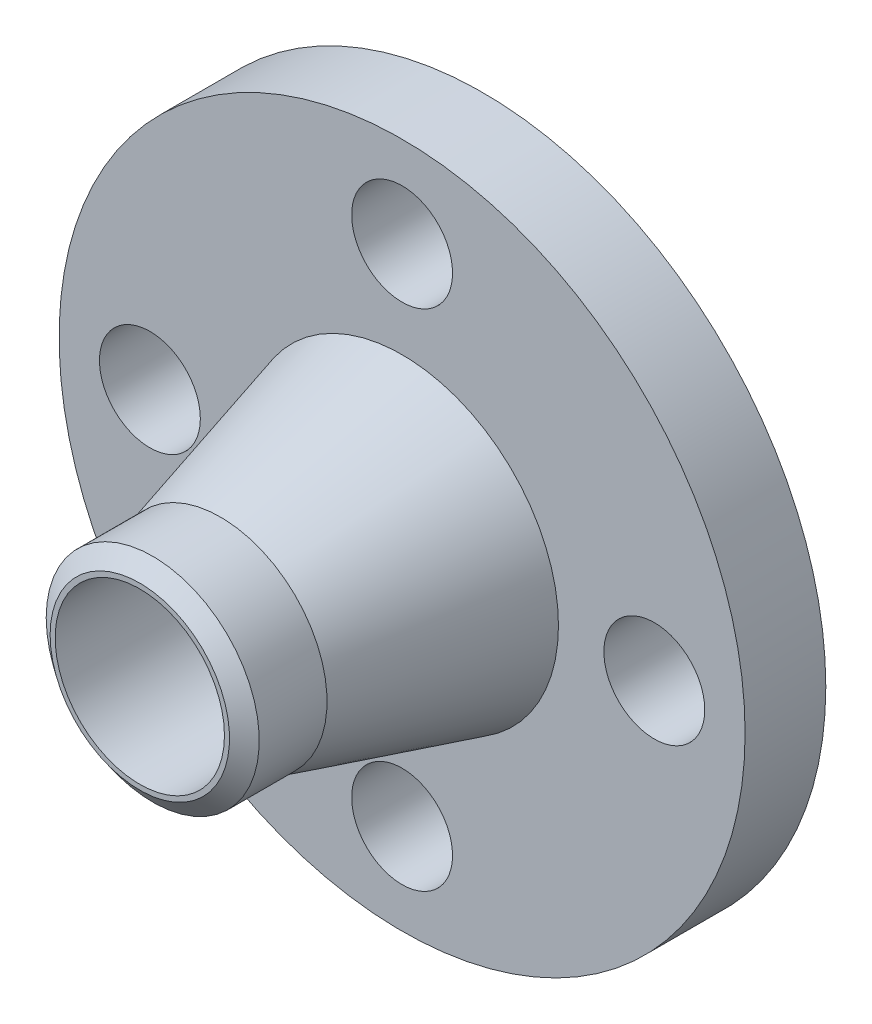
SolidWorks part; units mm, degrees
ref_plane "Front Plane" through (0, 0, 0) normal (0, 0, 1) x (1, 0, 0)
ref_plane "Top Plane" through (0, 0, 0) normal (0, 1, 0) x (1, 0, 0)
ref_plane "Right Plane" through (0, 0, 0) normal (1, 0, 0) x (0, 0, -1)
ref_axis "Axis1" through (0, 0, -2.6194) along (0, 0, 1)
sketch "Sketch1" plane through (0, 0, 0) normal (0, 0, 1) x (1, 0, 0)
  line L1 (0, 0) -> (0, 53.975) construction
  circle A0 centre (0, 0) radius 53.975
  circle A1 centre (0, 0) radius 39.6875 construction
  circle A2 centre (0, 39.6875) radius 7.9375
  circle A3 centre (0, 0) radius 16.764
  circle A6 centre (0, 0) radius 25.4
  circle A7 centre (0, 0) radius 24.6062
  dimension "Flange OD" = 107.95
  dimension "Bolt Circle" = 79.375
  dimension "Bolt Hole Size" = 15.875
  dimension "Raised Face Dia." = 50.8
  dimension "Hub Dia." = 49.2125
  dimension "A" = 33.528
sketch "Sketch2" plane through (0, 0, 0) normal (1, 0, 0) x (0, 0, -1)
  line L0 (0, 0) -> (-1.5875, 0) construction
  line L1 (-1.5875, 0) -> (-14.2875, 0) construction
  line L2 (-14.2875, 0) -> (-55.5625, 0) construction
  point P3 (-42.8625, 0)
  dimension "Raised Face Height" = 1.5875
  dimension "Thickness" = 14.2875
  dimension "Lenght Through Hub" = 55.5625
  dimension "Tangent" = 12.7
extrude "Extrude1" add sketch "Sketch1" along normal up to vertex (1.5875 mm away) contours A6 up to point (0, 0, 1.5875)
extrude "Extrude2" add sketch "Sketch1<3>" along normal up to vertex (14.2875 mm away) from vertex contours A0 up to point (0, 0, 14.2875) starting at point (0, 0, 1.5875)
sketch "Sketch1<3>" plane through (0, 0, 0) normal (0, 0, 1) x (1, 0, 0) same geometry as "Sketch1"
extrude "Extrude3" add sketch "Sketch1<4>" along normal up to vertex (55.5625 mm away) from vertex contours A3 up to point (0, 0, 55.5625) starting at point (0, 0, 14.2875)
sketch "Sketch1<4>" plane through (0, 0, 0) normal (0, 0, 1) x (1, 0, 0) same geometry as "Sketch1"
sketch "Sketch4" plane through (0, 0, 0) normal (1, 0, 0) x (0, 0, -1)
  line L0 (-42.8625, 0) -> (-42.8625, 16.764) construction
  line L1 (-14.2875, 16.764) -> (-55.5625, 16.764) construction
  line L2 (-42.8625, 16.764) -> (-14.2875, 24.6063)
  line L3 (-14.2875, 53.975) -> (-14.2875, -53.975) construction
  line L4 (-14.2875, 24.6063) -> (-14.2875, 16.764)
  line L5 (-14.2875, 16.764) -> (-42.8625, 16.764)
  line L6 (-14.2875, 24.6063) -> (0, 24.6063) construction
  line L9 (-42.8625, 0) -> (0, 0) construction
  line L10 (0, 0) -> (0, 24.6063) construction
revolve "Revolve1" add sketch "Sketch4" angle 360 about axis through (0, 0, -2.6194) along (0, 0, 1)
extrude "Extrude4" cut sketch "Sketch1<5>" along normal up to surface (14.2875 mm away) from surface contours A2 up to face at (24.6063, 0, 14.2875) starting at face at (53.975, 0, 1.5875)
sketch "Sketch1<5>" plane through (0, 0, 0) normal (0, 0, 1) x (1, 0, 0) same geometry as "Sketch1"
pattern_circular "CirPattern1" count 4 over 360 about axis through (0, 0, -2.6194) along (0, 0, 1) of "Extrude4"
sketch "Sketch3" plane through (0, 0, 55.5625) normal (0, 0, -1) x (-1, 0, 0)
  circle A0 centre (0, 0) radius 13.3223
  dimension "Bore" = 26.6446
extrude "Extrude5" cut sketch "Sketch3" along normal up to next
sketch "Sketch5" plane through (0, 0, 0) normal (1, 0, 0) x (0, 0, -1)
  line L0 (-55.5625, 16.764) -> (-53.5307, 16.764)
  line L1 (-53.5307, 16.764) -> (-55.5625, 14.116)
  line L2 (-55.5625, 16.764) -> (-55.5625, -16.764) construction
  line L3 (-55.5625, 14.116) -> (-55.5625, 16.764)
  point P3 (-55.5625, 13.3223)
  dimension "D1" = 37.5
  dimension "D2" = 0.7937
revolve "Cut-Revolve1" cut sketch "Sketch5" angle 360 about axis through (0, 0, -2.6194) along (0, 0, 1)
